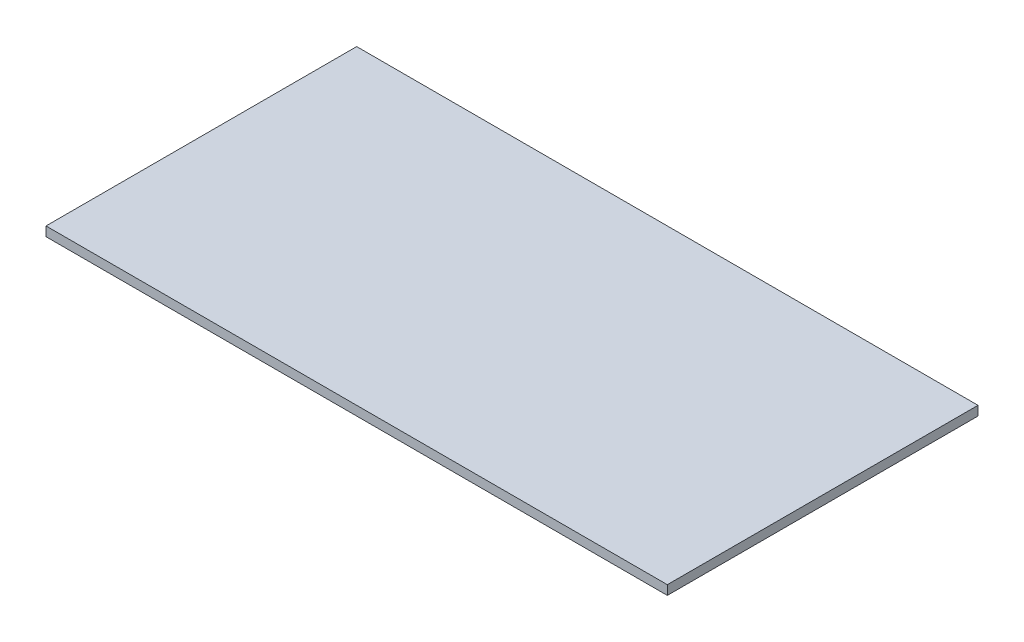
SolidWorks part; units mm, degrees
ref_plane "Спереди" through (0, 0, 0) normal (0, 0, 1) x (1, 0, 0)
ref_plane "Сверху" through (0, 0, 0) normal (0, 1, 0) x (1, 0, 0)
ref_plane "Справа" through (0, 0, 0) normal (1, 0, 0) x (0, 0, -1)
sketch "Эскиз1" plane through (0, 0, 0) normal (0, 1, 0) x (1, 0, 0)
  line L1 (-100, -50) -> (100, -50)
  line L2 (-100, -50) -> (-100, 50)
  line L3 (-100, 50) -> (100, 50)
  line L4 (100, -50) -> (100, 50)
  line L5 (-100, -50) -> (100, 50) construction
  line L6 (-100, 50) -> (100, -50) construction
  point P0 (0, 0)
extrude "abot_base" add sketch "Эскиз1" along normal blind 3
ref_plane "Плоскость1" through (-40, 0, 0) normal (-1, 0, 0) x (0, 0, 1)
ref_axis "Ось2" through (-40, 3, 55) along (0, 0, -1)
